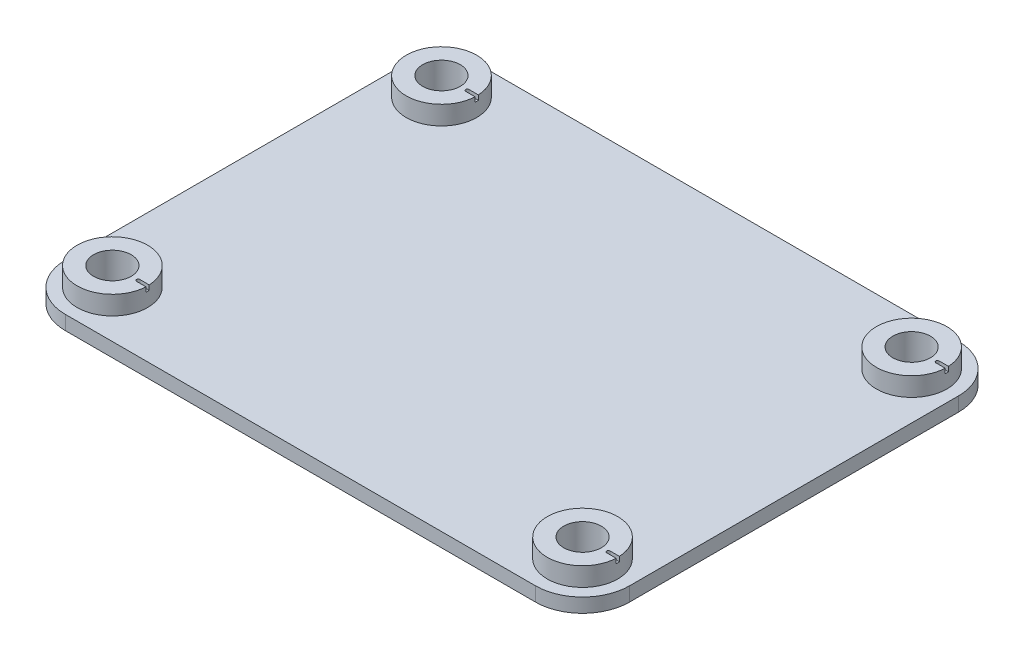
SolidWorks part; units mm, degrees
ref_plane "前视基准面" through (0, 0, 0) normal (0, 0, 1) x (1, 0, 0)
ref_plane "上视基准面" through (0, 0, 0) normal (0, 1, 0) x (1, 0, 0)
ref_plane "右视基准面" through (0, 0, 0) normal (1, 0, 0) x (0, 0, -1)
other "Configuration Table"
sketch "草图1" plane through (0, 0, 0) normal (0, 1, 0) x (1, 0, 0)
  line L1 (-500, -450) -> (500, -450)
  line L2 (-600, -350) -> (-600, 350)
  line L3 (-500, 450) -> (500, 450)
  line L4 (600, -350) -> (600, 350)
  line L5 (-600, -450) -> (600, 450) construction
  line L6 (-600, 450) -> (600, -450) construction
  arc A0 (500, -450) -> (600, -350) centre (500, -350) ccw
  arc A1 (-600, 350) -> (-500, 450) centre (-500, 350) cw
  arc A2 (-500, -450) -> (-600, -350) centre (-500, -350) cw
  arc A3 (500, 450) -> (600, 350) centre (500, 350) cw
  circle A4 centre (-500, 350) radius 30
  circle A5 centre (500, 350) radius 30
  circle A6 centre (-500, -350) radius 30
  circle A7 centre (500, -350) radius 30
  point P0 (0, 0)
  dimension "D3" = 100
  dimension "D4" = 60
  dimension "D5" = 60
  dimension "D6" = 60
  dimension "D7" = 60
  dimension "D1" = 1200
  dimension "D2" = 900
extrude "凸台-拉伸1" add sketch "草图1" along normal blind 10
sketch "草图2" plane through (0, 10, 0) normal (0, 1, 0) x (1, 0, 0)
  line L8 (600, -350) -> (600, 350)
  line L9 (500, 450) -> (-500, 450)
  line L10 (-600, 350) -> (-600, -350)
  line L11 (-500, -450) -> (500, -450)
  line L12 (600, -350) -> (600, 350)
  line L13 (500, 450) -> (-500, 450)
  line L14 (-600, 350) -> (-600, -350)
  line L15 (-500, -450) -> (500, -450)
  circle A4 centre (-500, 350) radius 40
  circle A5 centre (-500, -350) radius 40
  circle A6 centre (500, -350) radius 40
  circle A7 centre (500, 350) radius 40
  arc A8 (500, -450) -> (600, -350) centre (500, -350) ccw
  arc A9 (600, 350) -> (500, 450) centre (500, 350) ccw
  arc A10 (-500, 450) -> (-600, 350) centre (-500, 350) ccw
  arc A11 (-600, -350) -> (-500, -450) centre (-500, -350) ccw
  arc A12 (500, -450) -> (600, -350) centre (500, -350) ccw
  arc A13 (600, 350) -> (500, 450) centre (500, 350) ccw
  arc A14 (-500, 450) -> (-600, 350) centre (-500, 350) ccw
  arc A15 (-600, -350) -> (-500, -450) centre (-500, -350) ccw
  dimension "D2" = 80
  dimension "D3" = 80
  dimension "D4" = 80
  dimension "D5" = 80
  dimension "D1" = 0
extrude "凸台-拉伸2" add sketch "草图2" along normal blind 60
sketch "草图3" plane through (0, 70, 0) normal (0, 1, 0) x (1, 0, 0)
  line L8 (600, -350) -> (600, 350)
  line L9 (500, 450) -> (-500, 450)
  line L10 (-600, 350) -> (-600, -350)
  line L11 (-500, -450) -> (500, -450)
  line L12 (600, -350) -> (600, 350)
  line L13 (500, 450) -> (-500, 450)
  line L14 (-600, 350) -> (-600, -350)
  line L15 (-500, -450) -> (500, -450)
  circle A0 centre (-500, 350) radius 75
  circle A1 centre (-500, -350) radius 75
  circle A2 centre (500, 350) radius 75
  circle A3 centre (500, -350) radius 75
  arc A8 (500, -450) -> (600, -350) centre (500, -350) ccw
  arc A9 (600, 350) -> (500, 450) centre (500, 350) ccw
  arc A10 (-500, 450) -> (-600, 350) centre (-500, 350) ccw
  arc A11 (-600, -350) -> (-500, -450) centre (-500, -350) ccw
  arc A12 (500, -450) -> (600, -350) centre (500, -350) ccw
  arc A13 (600, 350) -> (500, 450) centre (500, 350) ccw
  arc A14 (-500, 450) -> (-600, 350) centre (-500, 350) ccw
  arc A15 (-600, -350) -> (-500, -450) centre (-500, -350) ccw
  dimension "D2" = 150
  dimension "D3" = 150
  dimension "D4" = 150
  dimension "D5" = 150
  dimension "D1" = 0
extrude "切除-拉伸1" cut sketch "草图3" against normal blind 40
sketch "草图7" plane through (0, 70, 0) normal (0, 1, 0) x (1, 0, 0)
  line L0 (-425, 350) -> (-445, 350) construction
  line L1 (-425, 346.5) -> (-445, 346.5)
  line L2 (-425, 353.5) -> (-445, 353.5)
  line L3 (575, 350) -> (555, 350) construction
  line L4 (575, 346.5) -> (555, 346.5)
  line L5 (575, 353.5) -> (555, 353.5)
  line L6 (575, -350) -> (555, -350) construction
  line L7 (575, -353.5) -> (555, -353.5)
  line L8 (575, -346.5) -> (555, -346.5)
  line L9 (-425, -350) -> (-445, -350) construction
  line L10 (-425, -353.5) -> (-445, -353.5)
  line L11 (-425, -346.5) -> (-445, -346.5)
  circle A0 centre (-500, 350) radius 75 construction
  circle A1 centre (-500, 350) radius 75 construction
  arc A2 (-425, 346.5) -> (-425, 353.5) centre (-425, 350) ccw
  arc A3 (-445, 353.5) -> (-445, 346.5) centre (-445, 350) ccw
  circle A4 centre (500, 350) radius 75 construction
  arc A5 (575, 346.5) -> (575, 353.5) centre (575, 350) ccw
  arc A6 (555, 353.5) -> (555, 346.5) centre (555, 350) ccw
  circle A7 centre (500, -350) radius 75 construction
  circle A8 centre (500, -350) radius 75 construction
  arc A9 (575, -353.5) -> (575, -346.5) centre (575, -350) ccw
  arc A10 (555, -346.5) -> (555, -353.5) centre (555, -350) ccw
  circle A11 centre (-500, -350) radius 75 construction
  circle A12 centre (-500, -350) radius 75 construction
  arc A13 (-425, -353.5) -> (-425, -346.5) centre (-425, -350) ccw
  arc A14 (-445, -346.5) -> (-445, -353.5) centre (-445, -350) ccw
  point P7 (-435, 350)
  point P17 (565, 350)
  point P22 (565, -350)
  point P33 (-435, -350)
  point P45 (565, -353.5)
  dimension "D1" = 20
  dimension "D2" = 7
  dimension "D3" = 20
  dimension "D4" = 7
  dimension "D5" = 20
  dimension "D6" = 7
  dimension "D7" = 20
  dimension "D8" = 7
extrude "切除-拉伸2" cut sketch "草图7" against normal blind 10
ref_axis "基准轴1" through (-500, 70, -350) along (0, -1, 0)
ref_axis "基准轴2" through (500, 70, -350) along (0, -1, 0)
ref_axis "基准轴3" through (500, 70, 350) along (0, -1, 0)
ref_axis "基准轴4" through (-500, 70, 350) along (0, -1, 0)
